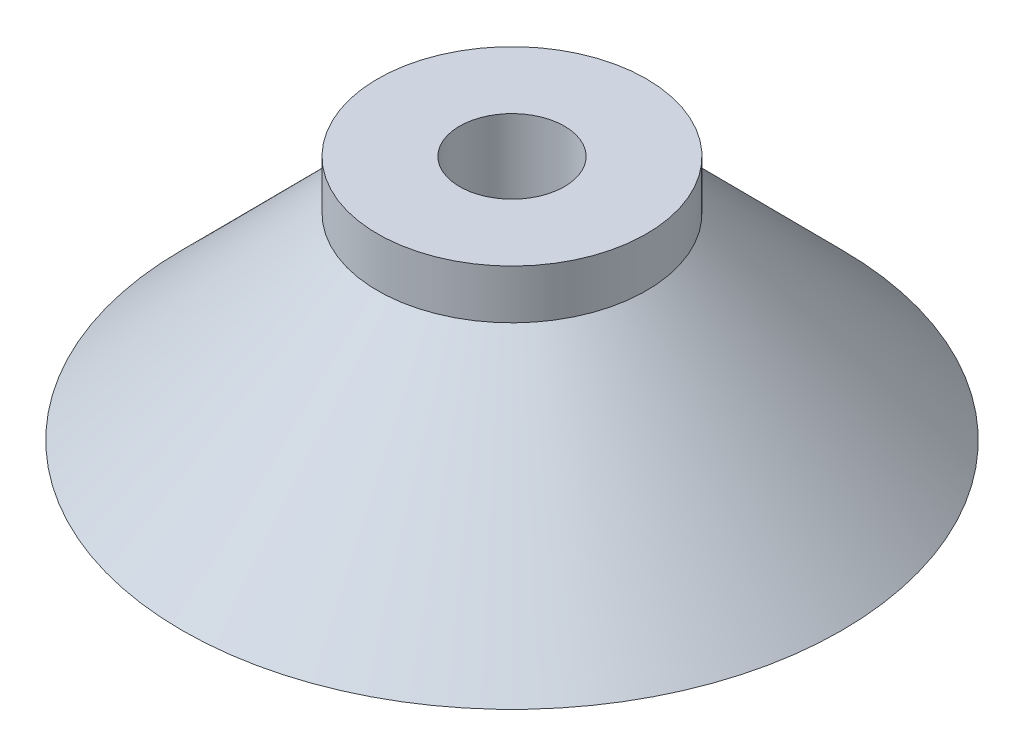
SolidWorks part; units mm, degrees
ref_plane "Front Plane" through (0, 0, 0) normal (0, 0, 1) x (1, 0, 0)
ref_plane "Top Plane" through (0, 0, 0) normal (0, 1, 0) x (1, 0, 0)
ref_plane "Right Plane" through (0, 0, 0) normal (1, 0, 0) x (0, 0, -1)
sketch "Sketch1" plane through (0, 0, 0) normal (1, 0, 0) x (0, 0, -1)
  line L0 (0, 0) -> (0, 9.525) construction
  line L1 (2.032, 0) -> (2.032, 9.525)
  line L2 (2.032, 9.525) -> (5.207, 9.525)
  line L3 (5.207, 9.525) -> (5.207, 7.62)
  line L4 (5.207, 7.62) -> (12.7762, 0)
  line L5 (12.7762, 0) -> (2.032, 0)
  dimension "D1" = 3.175
  dimension "D2" = 2.032
  dimension "D3" = 9.525
  dimension "D4" = 1.905
  dimension "D5" = 12.7762
revolve "Revolve1" add sketch "Sketch1" angle 360 about L0
